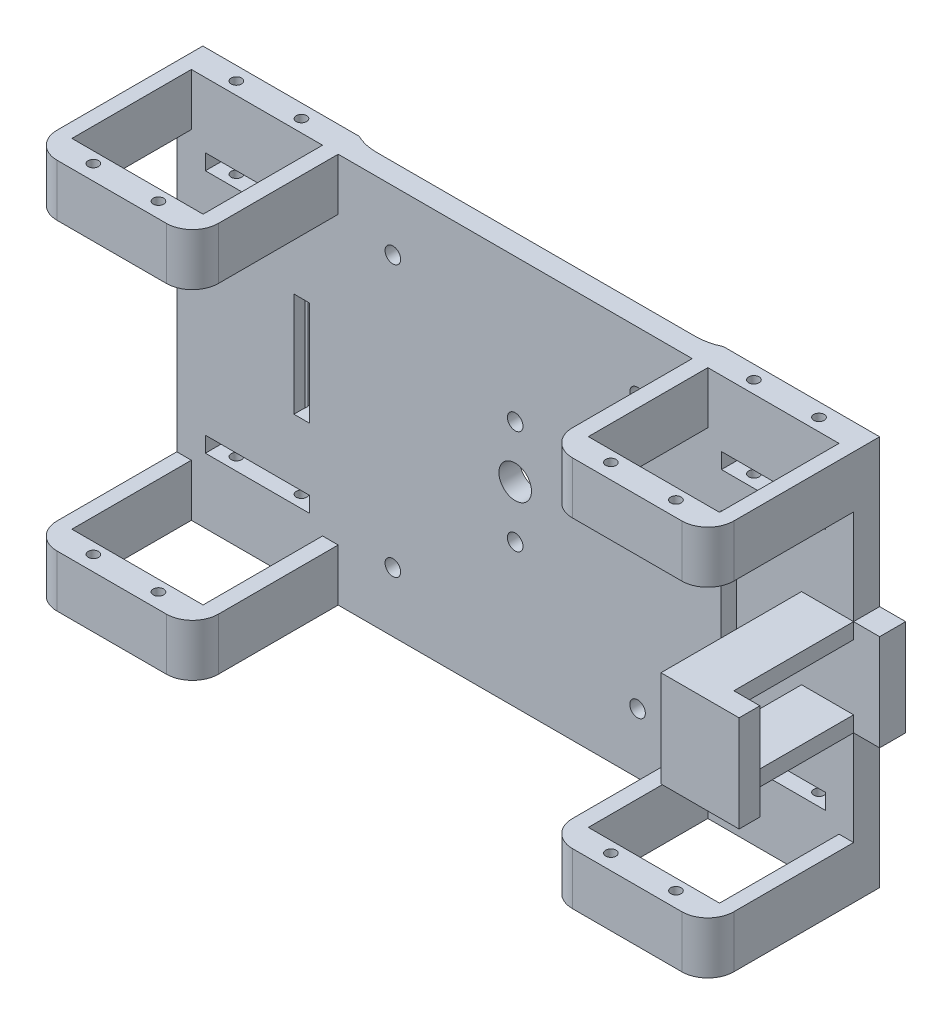
SolidWorks part; units mm, degrees
ref_plane "Front Plane" through (0, 0, 0) normal (0, 0, 1) x (1, 0, 0)
ref_plane "Top Plane" through (0, 0, 0) normal (0, 1, 0) x (1, 0, 0)
ref_plane "Right Plane" through (0, 0, 0) normal (1, 0, 0) x (0, 0, -1)
sketch "Sketch1" plane through (0, 0, 0) normal (0, 0, 1) x (1, 0, 0)
  line L1 (-65, -37.5) -> (65, -37.5)
  line L2 (-65, -37.5) -> (-65, 37.5)
  line L3 (-65, 37.5) -> (65, 37.5)
  line L4 (65, -37.5) -> (65, 37.5)
  line L5 (-65, -37.5) -> (65, 37.5) construction
  line L6 (-65, 37.5) -> (65, -37.5) construction
  point P0 (0, 0)
  dimension "D1" = 75
  dimension "D2" = 130
extrude "Boss-Extrude1" add sketch "Sketch1" along normal blind 4
sketch "Sketch2" plane through (0, 0, 4) normal (0, 0, 1) x (1, 0, 0)
  line L0 (18.15, 0) -> (-18.15, 0) construction
  line L1 (-65, 37.5) -> (-34, 37.5)
  line L2 (-65, 37.5) -> (-65, 27.5)
  line L3 (-65, 27.5) -> (-34, 27.5)
  line L4 (-34, 37.5) -> (-34, 27.5)
  line L5 (65, 37.5) -> (34, 37.5)
  line L6 (65, 37.5) -> (65, 27.5)
  line L7 (65, 27.5) -> (34, 27.5)
  line L8 (34, 37.5) -> (34, 27.5)
  line L9 (34, -37.5) -> (34, -27.5)
  line L10 (65, -27.5) -> (34, -27.5)
  line L11 (65, -37.5) -> (65, -27.5)
  line L12 (65, -37.5) -> (34, -37.5)
  line L13 (-34, -37.5) -> (-34, -27.5)
  line L14 (-65, -27.5) -> (-34, -27.5)
  line L15 (-65, -37.5) -> (-65, -27.5)
  line L16 (-65, -37.5) -> (-34, -37.5)
  dimension "D1" = 10
  dimension "D2" = 31
extrude "Boss-Extrude2" add sketch "Sketch2" along normal blind 28
sketch "Sketch3" plane through (0, -37.5, 0) normal (0, -1, 0) x (1, 0, 0)
  line L0 (-34, 4) -> (34, 4) construction
  line L1 (-62.2, 26.95) -> (-37, 26.95)
  line L2 (-62.2, 26.95) -> (-62.2, 4)
  line L3 (-62.2, 4) -> (-37, 4)
  line L4 (-37, 26.95) -> (-37, 4)
  line L5 (-34, 32) -> (-34, 4) construction
  line L6 (0, -18.15) -> (0, 18.15) construction
  line L7 (37, 26.95) -> (37, 4)
  line L8 (62.2, 4) -> (37, 4)
  line L9 (62.2, 26.95) -> (62.2, 4)
  line L10 (62.2, 26.95) -> (37, 26.95)
  dimension "D1" = 22.95
  dimension "D2" = 25.2
  dimension "D3" = 3
extrude "Cut-Extrude1" cut sketch "Sketch3" against normal blind 100
sketch "Sketch4" plane through (0, 0, 0) normal (0, 0, -1) x (-1, 0, 0)
  line L0 (65, -37.5) -> (-65, -37.5) construction
  line L1 (-65, 37.5) -> (-35, 37.5)
  line L2 (-65, 37.5) -> (-65, -37.5)
  line L3 (-65, -37.5) -> (-35, -37.5)
  line L4 (-35, 37.5) -> (-35, -37.5)
  line L6 (65, 37.5) -> (35, 37.5)
  line L7 (65, 37.5) -> (65, -37.5)
  line L8 (65, -37.5) -> (35, -37.5)
  line L9 (35, 37.5) -> (35, -37.5)
  dimension "D1" = 30
extrude "Boss-Extrude3" add sketch "Sketch4" along normal blind 1
sketch "Sketch5" plane through (0, -37.5, 0) normal (0, -1, 0) x (1, 0, 0)
  line L1 (-37, 26.95) -> (-62.2, 26.95) construction
  line L2 (-37, 4) -> (-37, 26.95) construction
  line L4 (-62.2, 26.95) -> (-62.2, 4) construction
  line L5 (-62.2, 4) -> (-37, 4) construction
  line L6 (0, -18.15) -> (0, 18.15) construction
  circle A0 centre (-43.45, 29.075) radius 1
  circle A1 centre (-43.45, 1.601) radius 1
  circle A2 centre (-55.95, 1.601) radius 1
  circle A3 centre (-55.95, 29.075) radius 1
  circle A4 centre (55.95, 29.075) radius 1
  circle A5 centre (55.95, 1.601) radius 1
  circle A6 centre (43.45, 1.601) radius 1
  circle A7 centre (43.45, 29.075) radius 1
  dimension "D1" = 2
  dimension "D2" = 2.125
  dimension "D3" = 6.45
  dimension "D4" = 6.25
  dimension "D5" = 2.399
extrude "Cut-Extrude2" cut sketch "Sketch5" against normal blind 111
fillet "Fillet1" radius 10 2 edges at (-35, 0, 0) (35, 0, 0)
fillet "Fillet2" radius 5 8 edges at (-34, -32.5, 32) (34, -32.5, 32) (65, -32.5, 32) (65, 32.5, 32) (34, 32.5, 32) (-34, 32.5, 32) (-65, 32.5, 32) (-65, -32.5, 32)
sketch "Sketch6" plane through (0, 0, 4) normal (0, 0, 1) x (1, 0, 0)
  line L0 (-39.5088, -24.9905) -> (-59.5088, -24.9905)
  line L1 (59.6195, -24.8541) -> (39.6195, -24.8541)
  line L2 (59.6195, -24.8541) -> (59.6195, -21.8541)
  line L3 (59.6195, -21.8541) -> (39.6195, -21.8541)
  line L4 (39.6195, -24.8541) -> (39.6195, -21.8541)
  line L5 (-39.5088, -24.9905) -> (-39.5088, -21.9905)
  line L6 (-39.5088, -21.9905) -> (-59.5088, -21.9905)
  line L7 (-59.5088, -24.9905) -> (-59.5088, -21.9905)
  line L8 (18.15, 0) -> (-18.15, 0) construction
  line L9 (-59.5088, 24.9905) -> (-59.5088, 21.9905)
  line L10 (-39.5088, 21.9905) -> (-59.5088, 21.9905)
  line L11 (-39.5088, 24.9905) -> (-39.5088, 21.9905)
  line L12 (39.6195, 24.8541) -> (39.6195, 21.8541)
  line L13 (59.6195, 21.8541) -> (39.6195, 21.8541)
  line L14 (59.6195, 24.8541) -> (59.6195, 21.8541)
  line L15 (59.6195, 24.8541) -> (39.6195, 24.8541)
  line L16 (-39.5088, 24.9905) -> (-59.5088, 24.9905)
  dimension "D1" = 3
  dimension "D2" = 20
extrude "Cut-Extrude3" cut sketch "Sketch6" against normal blind 11
sketch "Sketch7" plane through (0, 0, 4) normal (0, 0, 1) x (1, 0, 0)
  circle A0 centre (-23.5, -26) radius 1.5
  circle A1 centre (-23.5, 26) radius 1.5
  circle A2 centre (23.5, 26) radius 1.5
  circle A3 centre (23.5, -26) radius 1.5
  dimension "D1" = 3
extrude "Cut-Extrude4" cut sketch "Sketch7" against normal blind 10
sketch "Sketch8" plane through (0, 0, 0) normal (0, 0, -1) x (-1, 0, 0)
  line L0 (-39.5, -22) -> (-39.5, 22)
  line L1 (-37.5, -20) -> (37.5, -20)
  line L2 (-37.5, -20) -> (-37.5, 20)
  line L3 (-37.5, 20) -> (37.5, 20)
  line L4 (37.5, -20) -> (37.5, 20)
  line L5 (-37.5, -20) -> (37.5, 20) construction
  line L6 (-37.5, 20) -> (37.5, -20) construction
  line L7 (39.5, -10) -> (42.5, -10)
  line L8 (39.5, -10) -> (39.5, 10)
  line L9 (39.5, 10) -> (42.5, 10)
  line L10 (42.5, -10) -> (42.5, 10)
  line L11 (39.5, -10) -> (42.5, 10) construction
  line L12 (39.5, 10) -> (42.5, -10) construction
  line L13 (-42.5, -15) -> (-39.5, -15)
  line L14 (-42.5, -15) -> (-42.5, 15)
  line L15 (-42.5, 15) -> (-39.5, 15)
  line L16 (-39.5, -15) -> (-39.5, 15)
  line L17 (-42.5, -15) -> (-39.5, 15) construction
  line L18 (-42.5, 15) -> (-39.5, -15) construction
  line L19 (-39.5, 22) -> (39.5, 22)
  line L20 (39.5, -22) -> (39.5, 22)
  line L21 (-39.5, -22) -> (39.5, -22)
  circle A0 centre (0, 10) radius 1.5
  circle A1 centre (0, -10) radius 1.5
  point P0 (0, 0)
  point P8 (-41, 0)
  point P9 (41, 0)
  point P12 (0, 20)
  line M8 (30.6411, -37.5) -> (30.6411, 37.5)
  line M10 (-30.6411, 37.5) -> (-30.6411, -37.5)
  dimension "D4" = 3
  dimension "D5" = 3
  dimension "D1" = 40
  dimension "D2" = 75
  dimension "D3" = 10
  dimension "D6" = 10
  dimension "D7" = 20
  dimension "D8" = 3
  dimension "D9" = 2
  dimension "D10" = 30
  dimension "D11" = 2
  dimension "D12" = 2
extrude "Cut-Extrude5" cut sketch "Sketch8" against normal blind 10 and the other way blind 10 contours A0 | A1 | L7 L10 L9 L8 | L13 L16 L15 L14 region at (41, 0, 0) region at (-41, 0, 0) region at (0, 10, 0) region at (0, -10, 0)
extrude "Cut-Extrude6" cut sketch "Sketch8<3>" along normal blind 10 contours L3 L2 L1 M10 | L0 L21 L1 L2 L3 L19 M10 | L3 L1 A1 A0 M10 M8 | L19 L3 M10 M8 | L1 L4 L3 M8 | L21 L20 L8 L19 L3 L4 L1 M8 | L21 L1 M10 M8 region at (39.0512, -18.5, 0) region at (0, -21, 0) region at (-31.0899, -21, 0) region at (0, 0, 0) region at (34.0706, 0, 0) region at (-34.0706, 0, 0) region at (0, 21, 0)
sketch "Sketch8<3>" plane through (0, 0, 0) normal (0, 0, -1) x (-1, 0, 0) same geometry as "Sketch8"
sketch "Sketch9" plane through (0, 0, -1) normal (0, 0, -1) x (-1, 0, 0)
  line L0 (-50, 26.7) -> (-50, 35.7) construction
  line L1 (-52.5, 26.7) -> (-52.5, 35.7)
  line L2 (-47.5, 26.7) -> (-47.5, 35.7)
  line L3 (0, 18.15) -> (0, -18.15) construction
  line L4 (50, 26.7) -> (50, 35.7) construction
  line L5 (52.5, 26.7) -> (52.5, 35.7)
  line L6 (47.5, 26.7) -> (47.5, 35.7)
  line L7 (18.15, 0) -> (-18.15, 0) construction
  line L8 (-50, -26.7) -> (-50, -35.7) construction
  line L9 (-52.5, -26.7) -> (-52.5, -35.7)
  line L10 (-47.5, -26.7) -> (-47.5, -35.7)
  line L11 (50, -26.7) -> (50, -35.7) construction
  line L12 (39.5, 22) -> (39.5, 10)
  line L13 (39.5, 10) -> (42.5, 10)
  line L14 (42.5, 10) -> (42.5, -10)
  line L15 (42.5, -10) -> (39.5, -10)
  line L16 (39.5, -10) -> (39.5, -22)
  line L17 (39.5, -22) -> (35, -22)
  line L18 (35, -22) -> (35, -37.5)
  line L19 (35, -37.5) -> (65, -37.5)
  line L20 (65, -37.5) -> (65, 37.5)
  line L21 (65, 37.5) -> (35, 37.5)
  line L22 (35, 37.5) -> (35, 22)
  line L23 (35, 22) -> (39.5, 22)
  line L24 (39.5, 22) -> (39.5, 10)
  line L25 (39.5, 10) -> (42.5, 10)
  line L26 (42.5, 10) -> (42.5, -10)
  line L27 (42.5, -10) -> (39.5, -10)
  line L28 (39.5, -10) -> (39.5, -22)
  line L29 (39.5, -22) -> (35, -22)
  line L30 (35, -22) -> (35, -37.5)
  line L31 (35, -37.5) -> (65, -37.5)
  line L32 (65, -37.5) -> (65, 37.5)
  line L33 (65, 37.5) -> (35, 37.5)
  line L34 (35, 37.5) -> (35, 22)
  line L35 (35, 22) -> (39.5, 22)
  line L36 (-39.5, 22) -> (-35, 22)
  line L37 (-35, 22) -> (-35, 37.5)
  line L38 (-35, 37.5) -> (-65, 37.5)
  line L39 (-65, 37.5) -> (-65, -37.5)
  line L40 (-65, -37.5) -> (-35, -37.5)
  line L41 (-35, -37.5) -> (-35, -22)
  line L42 (-35, -22) -> (-39.5, -22)
  line L43 (-39.5, -22) -> (-39.5, -15)
  line L44 (-39.5, -15) -> (-42.5, -15)
  line L45 (-42.5, -15) -> (-42.5, 15)
  line L46 (-42.5, 15) -> (-39.5, 15)
  line L47 (-39.5, 15) -> (-39.5, 22)
  line L48 (-39.5, 22) -> (-35, 22)
  line L49 (-35, 22) -> (-35, 37.5)
  line L50 (-35, 37.5) -> (-65, 37.5)
  line L51 (-65, 37.5) -> (-65, -37.5)
  line L52 (-65, -37.5) -> (-35, -37.5)
  line L53 (-35, -37.5) -> (-35, -22)
  line L54 (-35, -22) -> (-39.5, -22)
  line L55 (-39.5, -22) -> (-39.5, -15)
  line L56 (-39.5, -15) -> (-42.5, -15)
  line L57 (-42.5, -15) -> (-42.5, 15)
  line L58 (-42.5, 15) -> (-39.5, 15)
  line L59 (-39.5, 15) -> (-39.5, 22)
  line L60 (52.5, -26.7) -> (52.5, -35.7)
  line L61 (47.5, -26.7) -> (47.5, -35.7)
  arc A0 (-52.5, 26.7) -> (-47.5, 26.7) centre (-50, 26.7) ccw
  arc A1 (-47.5, 35.7) -> (-52.5, 35.7) centre (-50, 35.7) ccw
  circle A2 centre (-50, 35.7) radius 1
  circle A3 centre (-50, 26.7) radius 1
  arc A4 (52.5, 26.7) -> (47.5, 26.7) centre (50, 26.7) cw
  arc A5 (47.5, 35.7) -> (52.5, 35.7) centre (50, 35.7) cw
  circle A6 centre (50, 26.7) radius 1
  circle A7 centre (50, 35.7) radius 1
  arc A8 (-52.5, -26.7) -> (-47.5, -26.7) centre (-50, -26.7) cw
  arc A9 (-47.5, -35.7) -> (-52.5, -35.7) centre (-50, -35.7) cw
  arc A10 (52.5, -26.7) -> (47.5, -26.7) centre (50, -26.7) ccw
  arc A11 (47.5, -35.7) -> (52.5, -35.7) centre (50, -35.7) ccw
  circle A12 centre (50, -35.7) radius 1
  circle A13 centre (50, -26.7) radius 1
  circle A14 centre (-50, -26.7) radius 1
  circle A15 centre (-50, -35.7) radius 1
  point P14 (-50, 31.2)
  point P30 (-50, 37.5)
  point P41 (50, 31.2)
  point P54 (-50, -31.2)
  point P61 (50, -31.2)
  dimension "D3" = 2.5
  dimension "D6" = 2
  dimension "D4" = 6.3
  dimension "D5" = 9
  dimension "D1" = 0
  dimension "D2" = 0
extrude "Cut-Extrude7" cut sketch "Sketch9" against normal blind 3 and the other way blind 10 contours A2 | A3 | A7 | A6 | A12 | A15 | A14 | A13 region at (50, 35.7, -1) region at (50, 26.7, -1) region at (-50, 26.7, -1) region at (-50, 35.7, -1) region at (-50, -35.7, -1) region at (50, -26.7, -1) region at (50, -35.7, -1)
fillet "Fillet3" radius 0.5 16 edges at (-35.0706, -22, 0) (-37.25, -22, -1) (-39.5, -16, 0) (-39.5, -16, -1) (-39.5, 16, 0) (-39.5, 16, -1) (-35.0706, 22, 0) (-37.25, 22, -1) (35.0706, 22, 0) (37.25, 22, -1) (35.0706, -22, 0) (37.25, -22, -1) (39.5, -18.5, -1) (39.5, -18.5, 0) (39.5, 18.5, 0) (39.5, 18.5, -1)
sketch "Sketch11" plane through (0, 0, 4) normal (0, 0, 1) x (1, 0, 0)
  line L0 (65, 16.0068) -> (65, 27.5) construction
  line L1 (65, -9.25) -> (55, -9.25)
  line L2 (65, -9.25) -> (65, 9.25)
  line L3 (65, 9.25) -> (55, 9.25)
  line L4 (55, -9.25) -> (55, 9.25)
  line L5 (65, -9.25) -> (55, 9.25) construction
  line L6 (65, 9.25) -> (55, -9.25) construction
  line L7 (65, -6.25) -> (55, -6.25)
  line L8 (65, -6.25) -> (65, 6.25)
  line L9 (65, 6.25) -> (55, 6.25)
  line L10 (55, -6.25) -> (55, 6.25)
  line L11 (65, -6.25) -> (55, 6.25) construction
  line L12 (65, 6.25) -> (55, -6.25) construction
  point P0 (60, 0)
  point P5 (60, 0)
  dimension "D1" = 3
  dimension "D2" = 12.5
  dimension "D3" = 10
extrude "Boss-Extrude8" add sketch "Sketch11" along normal blind 27 contours L9 L2 L3 L4 | L2 L7 L4 L1 region at (60, -7.75, 4) region at (60, 7.75, 4)
sketch "Sketch13" plane through (0, -6.25, 0) normal (0, 1, 0) x (1, 0, 0)
  line L0 (55, -31) -> (55, -4) construction
  line L1 (65, -31) -> (55, -31)
  line L2 (65, -31) -> (65, -27)
  line L3 (65, -27) -> (55, -27)
  line L4 (55, -31) -> (55, -27)
  dimension "D1" = 4
extrude "Boss-Extrude9" add sketch "Sketch13" along normal blind 14
sketch "Sketch14" plane through (65, 0, 0) normal (1, 0, 0) x (0, 0, -1)
  line L0 (-31, 9.25) -> (-4, 9.25) construction
  line L1 (-31, -9.25) -> (-27, -9.25)
  line L2 (-31, -9.25) -> (-31, 9.25)
  line L3 (-31, 9.25) -> (-27, 9.25)
  line L4 (-27, -9.25) -> (-27, 9.25)
  line L5 (1, 37.5) -> (1, -37.5) construction
  line L6 (-4, -9.25) -> (1, -9.25)
  line L7 (-4, -9.25) -> (-4, 9.25)
  line L8 (-4, 9.25) -> (1, 9.25)
  line L9 (1, -9.25) -> (1, 9.25)
  line L10 (-27, 6.25) -> (-27, -6.25) construction
extrude "Boss-Extrude10" add sketch "Sketch14" along normal blind 5
sketch "Sketch15" plane through (0, 0, 4) normal (0, 0, 1) x (1, 0, 0)
  circle A0 centre (0, 0) radius 3.1268
extrude "Cut-Extrude8" cut sketch "Sketch15" against normal blind 5
